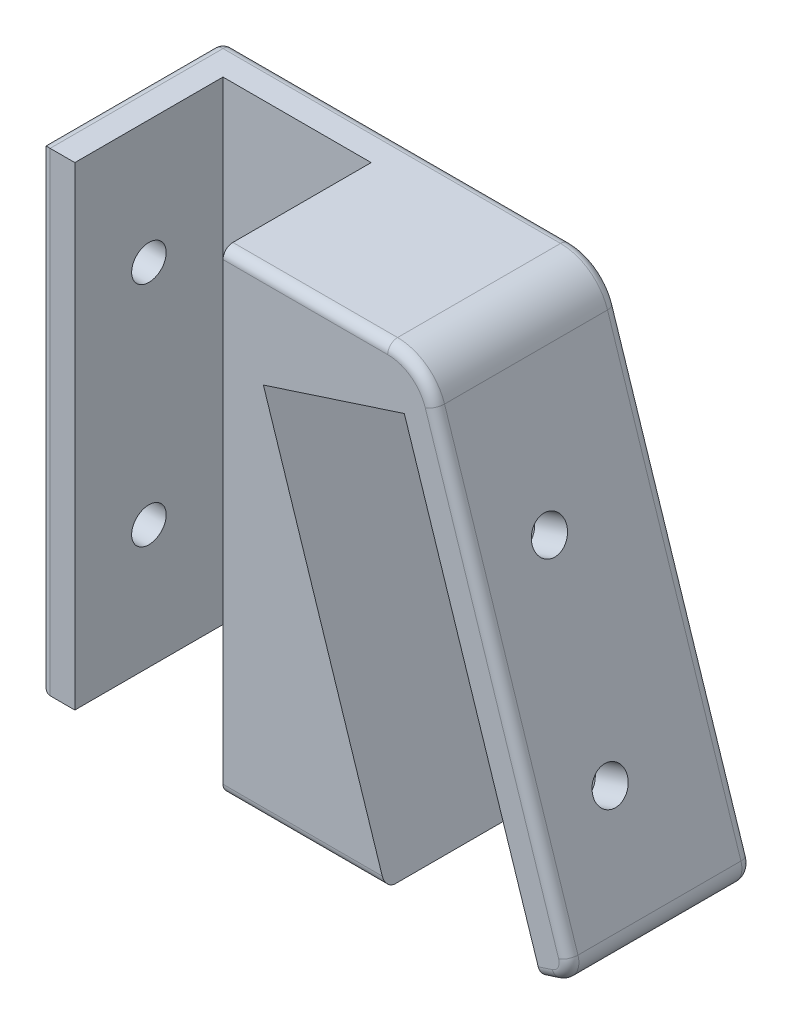
SolidWorks part; units mm, degrees
ref_plane "Front Plane" through (0, 0, 0) normal (0, 0, 1) x (1, 0, 0)
ref_plane "Top Plane" through (0, 0, 0) normal (0, 1, 0) x (1, 0, 0)
ref_plane "Right Plane" through (0, 0, 0) normal (1, 0, 0) x (0, 0, -1)
sketch "Sketch1" plane through (0, 0, 0) normal (0, 0, 1) x (1, 0, 0)
  line L0 (24.2599, 13.8081) -> (39.8561, -34.1919)
  line L2 (-14.5466, 13.8081) -> (-14.5466, -34.1919)
  line L3 (-14.5466, -34.1919) -> (7.4534, -34.1919)
  line L4 (7.4534, 38.3398) -> (7.4534, -34.1919) construction
  line L5 (39.8561, -34.1919) -> (7.4534, -34.1919)
  line L6 (16.7239, -34.1919) -> (7.4534, -5.6602) construction
  line L7 (7.4534, -5.6602) -> (67.3707, 13.8081) construction
  line L8 (24.2599, 13.8081) -> (-14.5466, 13.8081)
  dimension "D1" = 22
  dimension "D2" = 18
  dimension "D3" = 22
  dimension "D4" = 30
  dimension "D5" = 48
extrude "Boss-Extrude1" add sketch "Sketch1" along normal blind 18.5
sketch "Sketch2" plane through (0, 0, 18.5) normal (0, 0, 1) x (1, 0, 0)
  line L1 (-14.5466, -34.1919) -> (39.8561, -34.1919) construction
  line L2 (-11.0466, 13.8081) -> (3.9534, 13.8081)
  line L3 (-11.0466, 13.8081) -> (-11.0466, -34.1919)
  line L4 (-11.0466, -34.1919) -> (3.9534, -34.1919)
  line L5 (3.9534, 13.8081) -> (3.9534, -34.1919)
  line L6 (-14.5466, 13.8081) -> (-14.5466, -34.1919) construction
  line L7 (36.176, -34.1919) -> (22.3092, 8.4856)
  line L8 (22.3092, 8.4856) -> (8.0433, 3.8504)
  line L9 (8.0433, 3.8504) -> (20.404, -34.1919)
  line L10 (20.404, -34.1919) -> (36.176, -34.1919)
  line L11 (39.8561, -34.1919) -> (24.2599, 13.8081) construction
  line L12 (24.2599, 13.8081) -> (-14.5466, 13.8081) construction
  dimension "D1" = 15
  dimension "D2" = 3.5
  dimension "D3" = 3.5
  dimension "D4" = 15
  dimension "D5" = 40
extrude "Cut-Extrude1" cut sketch "Sketch2" against normal offset from surface (15 mm away) 3.5 up to face at (8.7557, -10.1919, 0)
sketch "Sketch3" plane through (26.0014, 8.4484, 0) normal (0.9511, 0.309, 0) x (0, 0, -1)
  line L0 (-11, 30.2721) -> (-11, -44.8346) construction
  line L1 (-3.5, 1.1764) -> (-18.5, 1.1764) construction
  line L2 (-18.5, -44.8346) -> (0, -44.8346) construction
  line L3 (-3.5, -43.6974) -> (-18.5, -43.6974) construction
  circle A0 centre (-11, -31.1974) radius 1.75
  circle A2 centre (-11, -11.3236) radius 1.75
  dimension "D1" = 3.5
  dimension "D2" = 12.5
  dimension "D3" = 12.5
extrude "Cut-Extrude2" cut sketch "Sketch3" against normal blind 3.5
sketch "Sketch4" plane through (0, 0, 0) normal (0, 0, -1) x (-1, 0, 0)
  line L0 (3.5466, 13.8081) -> (3.5466, -34.1919) construction
  line L1 (-36.176, -34.1919) -> (-20.404, -34.1919) construction
  line L2 (14.5466, -34.1919) -> (-39.8561, -34.1919) construction
  line L3 (-15.1763, 6.168) -> (-28.29, -34.1919) construction
  line L4 (-8.0433, 3.8504) -> (-22.3092, 8.4856) construction
  line L5 (11.0466, 13.8081) -> (-3.9534, 13.8081) construction
  line L6 (-36.176, -34.1919) -> (-20.404, -34.1919) construction
  circle A0 centre (-24.4273, -22.3037) radius 1.75
  circle A2 centre (-19.039, -5.7202) radius 1.75
  circle A4 centre (3.5466, 1.3081) radius 1.75
  circle A6 centre (3.5466, -21.6919) radius 1.75
  circle A7 centre (3.5466, 12.8081) radius 1.75 [skipped]
  circle A8 centre (3.5466, -10.1919) radius 1.75 [skipped]
  dimension "D1" = 12.5
  dimension "D2" = 12.5
  dimension "D4" = 3.5
  dimension "D5" = 4
  dimension "D6" = 12.5
  dimension "D7" = 12.5
extrude "Cut-Extrude3" cut sketch "Sketch4" against normal blind 4
sketch "Sketch5" plane through (-14.5466, 0, 0) normal (-1, 0, 0) x (0, 0, 1)
  line L0 (11, 13.8081) -> (11, -34.1919) construction
  line L2 (18.5, -34.1919) -> (0, -34.1919) construction
  line L3 (18.5, 13.8081) -> (18.5, -34.1919) construction
  line L4 (18.5, 13.8081) -> (0, 13.8081) construction
  circle A0 centre (11, -21.6919) radius 1.75
  circle A2 centre (11, 1.3081) radius 1.75
  circle A4 centre (11, 12.8081) radius 1.75 [skipped]
  circle A5 centre (11, -10.1919) radius 1.75 [skipped]
  dimension "D2" = 3.5
  dimension "D3" = 12.5
  dimension "D5" = 12.5
  dimension "D1" = 7.5
  dimension "D4" = 4
extrude "Cut-Extrude4" cut sketch "Sketch5" against normal blind 4
sketch "Sketch6" plane through (0, 0, 18.5) normal (0, 0, 1) x (1, 0, 0)
  line L0 (36.176, -34.1919) -> (39.5047, -33.1103)
  line L1 (39.8561, -34.1919) -> (24.2599, 13.8081) construction
  line L2 (39.5047, -33.1103) -> (39.8561, -34.1919)
  line L3 (39.8561, -34.1919) -> (36.176, -34.1919)
extrude "Cut-Extrude5" cut sketch "Sketch6" against normal blind 19
fillet "Fillet1" radius 2 1 edges at (39.5047, -33.1103, 9.25)
fillet "Fillet2" radius 5 1 edges at (24.2599, 13.8081, 9.25)
fillet "Fillet3" radius 1 16 edges at (36.8893, -33.9601, 18.5) (38.7665, -32.7342, 18.5) (32.1346, -10.4275, 18.5) (23.5661, 12.8532, 18.5) (36.8893, -33.9601, 0) (38.7665, -32.7342, 0) (32.1346, -10.4275, 0) (23.5661, 12.8532, 0) (12.1787, -34.1919, 18.5) (12.2903, 13.8081, 18.5) (-14.5466, -34.1919, 9.25) (-14.5466, 13.8081, 9.25) (-14.5466, -10.1919, 18.5) (10.8147, -34.1919, 0) (3.0403, 13.8081, 0) (-14.5466, -10.1919, 0)
